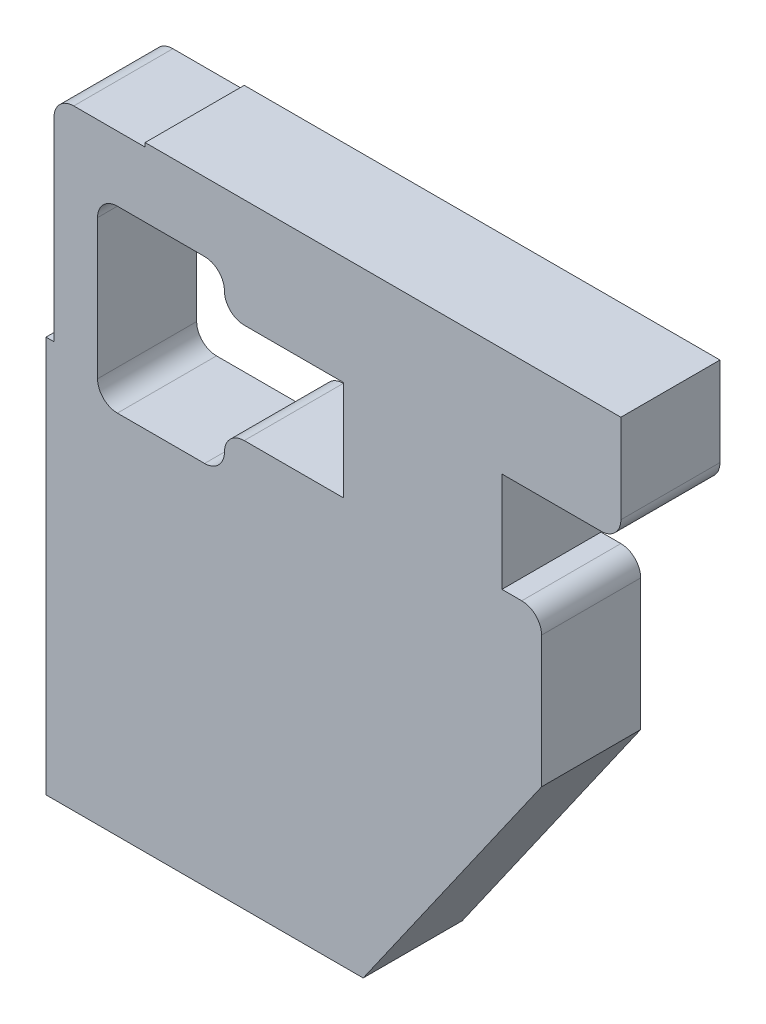
SolidWorks part; units mm, degrees
material "PBT General Purpose"
ref_plane "Front Plane" through (0, 0, 0) normal (0, 0, 1) x (1, 0, 0)
ref_plane "Top Plane" through (0, 0, 0) normal (0, 1, 0) x (1, 0, 0)
ref_plane "Right Plane" through (0, 0, 0) normal (1, 0, 0) x (0, 0, -1)
sketch "frame_outline" plane through (0, 0, 0) normal (0, 0, 1) x (1, 0, 0)
  line L0 (0, 0) -> (0, -0.6) construction
  line L1 (0, 0) -> (0.3, 0) construction
  line L2 (0, -0.6) -> (0.05, -0.6) construction
  line L3 (0.3, 0) -> (0.3, -0.05) construction
  line L8 (0.3, -0.05) -> (1.5, -0.05)
  line L19 (0.3, -0.05) -> (0.3, -0.06)
  line L20 (0.3, -0.06) -> (0.07, -0.06)
  line L21 (0.07, -0.06) -> (0.07, -0.6)
  line L62 (0.05, -0.6) -> (0.07, -0.6)
  line L63 (0.05, -0.6) -> (0.05, -1.6)
  line L64 (0.05, -1.6) -> (0.85, -1.6)
  line L65 (0.85, -1.6) -> (1.3, -0.9573)
  line L66 (1.3, -0.9573) -> (1.3, -0.576)
  line L67 (1.3, -0.576) -> (1.2, -0.576)
  line L68 (1.2, -0.576) -> (1.2, -0.324)
  line L69 (1.2, -0.324) -> (1.5, -0.324)
  line L70 (1.5, -0.324) -> (1.5, -0.05)
  line L71 (0, -0.45) -> (1.8135, -0.45) construction
  line L72 (0.5, -0.324) -> (0.8, -0.324)
  line L73 (0.8, -0.324) -> (0.8, -0.576)
  line L74 (0.8, -0.576) -> (0.5, -0.576)
  line L75 (0.5, -0.576) -> (0.5, -0.676)
  line L76 (0.5, -0.676) -> (0.18, -0.676)
  line L77 (0.18, -0.676) -> (0.18, -0.224)
  line L78 (0.18, -0.224) -> (0.5, -0.224)
  line L79 (0.5, -0.224) -> (0.5, -0.324)
  line L80 (1.2, -0.05) -> (1.2, -1.1001) construction
  point P22 (1.2, -0.45)
  dimension "D2" = 0.3
  dimension "D6" = 1.2
  dimension "D4" = 0.05
  dimension "D1" = 0.05
  dimension "D3" = 0.6
  dimension "D5" = 0.02
  dimension "D7" = 0.01
  dimension "D8" = 1
  dimension "D9" = 0.45
  dimension "D10" = 0.252
  dimension "D11" = 0.1
  dimension "D12" = 0.32
  dimension "D13" = 0.3
  dimension "D14" = 0.1
  dimension "D15" = 0.4
  dimension "D16" = 0.85
  dimension "D17" = 55
  dimension "D18" = 0.3
extrude "Boss-Extrude1" add sketch "frame_outline" along normal mid plane 0.25
fillet "Fillet1" radius 0.05 9 edges at (1.3, -0.576, 0) (1.5, -0.324, 0) (0.5, -0.324, 0) (0.5, -0.576, 0) (0.5, -0.676, 0) (0.18, -0.676, 0) (0.5, -0.224, 0) (0.18, -0.224, 0) (0.07, -0.06, 0)
equation "\"t\"= 0.25'thickness of the sheets"
equation "\"t_cf\"= 0.115'thickness of single carbon fiber layer"
equation "\"t_kapton\"= 0.025'thickness of single Kapton flex layer"
equation "\"t_fr4\"= 0.1'thickness of FR4 with copper layer"
equation "\"joint_flex\"= 0.1'Width of flextures gap"
equation "\"joint_flex_eff\"= 0.02'Width of flecture after castelation"
equation "\"joint_fold\"= 0.2'Width of folding joints for 90deg fold"
equation "\"gap_tolerance\"= 0.002'Width to have interfecence fit between carbon fiber inserts"
equation "\"assemble_angle\"= 90'Angle of assembly parts"
equation "\"D1@Boss-Extrude1\"=\"t\""
equation "\"link_lift\"= 0.5'Actuation linkage amplification for the lift motion"
equation "\"link_swing\"= 0.45'Actuation linkage amplification for the swing motion"
equation "\"D9@frame_outline\"=\"link_swing\""
equation "\"D4@frame_outline\"=\"joint_flex\"/2"
equation "\"D1@frame_outline\"=\"joint_flex\"/2"
equation "\"D10@frame_outline\"=\"t\"+\"gap_tolerance\""
